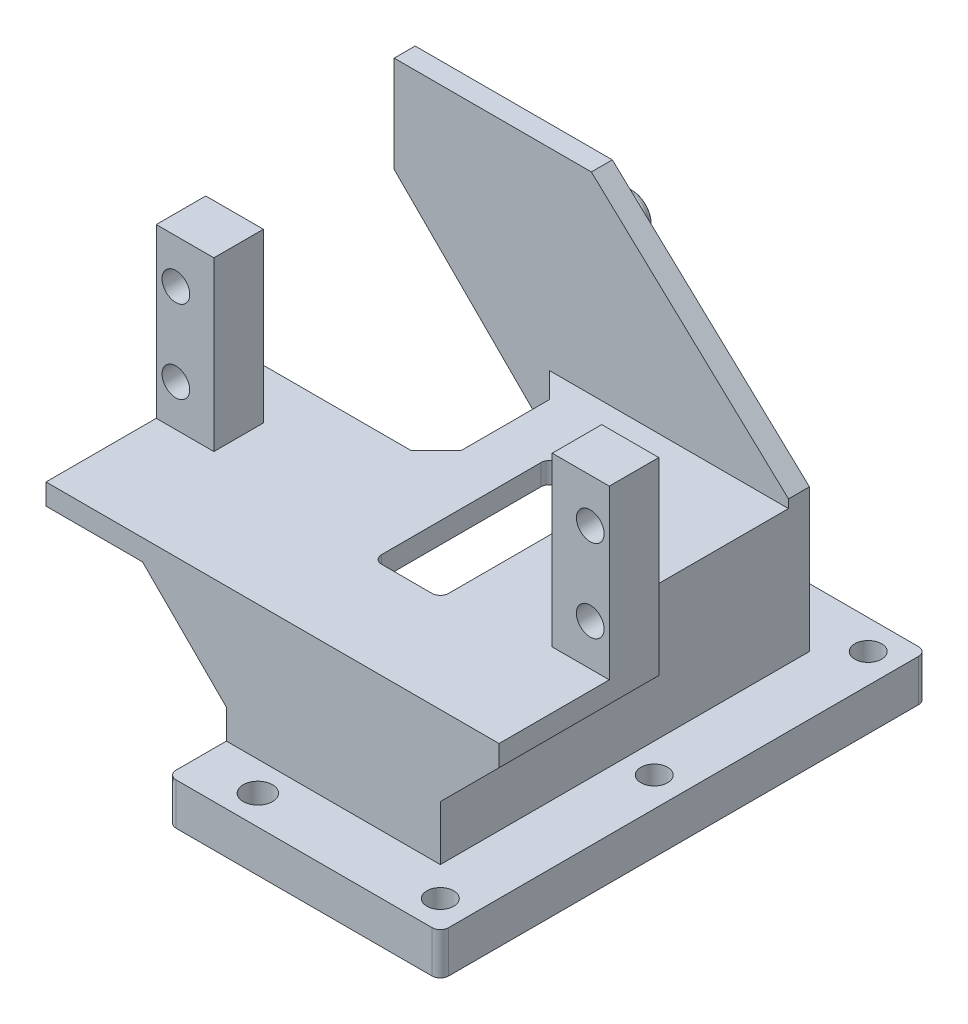
SolidWorks part; units mm, degrees
ref_plane "Front Plane" through (0, 0, 0) normal (0, 0, 1) x (1, 0, 0)
ref_plane "Top Plane" through (0, 0, 0) normal (0, 1, 0) x (1, 0, 0)
ref_plane "Right Plane" through (0, 0, 0) normal (1, 0, 0) x (0, 0, -1)
sketch "Sketch1" plane through (0, 0, 0) normal (0, 1, 0) x (1, 0, 0)
  line L0 (0, 40) -> (23, 40)
  line L1 (30, 0) -> (80, 0)
  line L2 (0, 20) -> (0, 40)
  line L3 (0, 100) -> (110, 100)
  line L4 (110, 20) -> (110, 40)
  line L5 (23, 40) -> (23, 79)
  line L6 (23, 79) -> (0, 79)
  line L7 (110, 79) -> (87, 79)
  line L8 (87, 79) -> (87, 40)
  line L9 (87, 40) -> (110, 40)
  line L10 (0, 79) -> (0, 100)
  line L11 (110, 79) -> (110, 100)
  line L12 (0, 20) -> (30, 0)
  line L13 (110, 20) -> (80, 0)
  point P0 (55, 0)
  dimension "D1" = 100
  dimension "D2" = 110
  dimension "23" = 23
  dimension "D4" = 40
  dimension "20" = 23
  dimension "D5" = 39
  dimension "40" = 40
extrude "Boss-Extrude1" add sketch "Sketch1" along normal blind 3.5
sketch "Sketch2" plane through (0, 3.5, 0) normal (0, 1, 0) x (1, 0, 0)
  line L0 (0, 79) -> (23, 79)
  line L1 (23, 79) -> (23, 40)
  line L2 (23, 40) -> (0, 40)
  line L3 (0, 40) -> (0, 37.5)
  line L4 (0, 40) -> (0, 20) construction
  line L5 (0, 37.5) -> (25.5, 37.5)
  line L6 (25.5, 37.5) -> (25.5, 81.5)
  line L7 (25.5, 81.5) -> (0, 81.5)
  line L8 (0, 100) -> (0, 79) construction
  line L9 (0, 81.5) -> (0, 79)
  line L10 (110, 81.5) -> (84.5, 81.5)
  line L11 (110, 79) -> (110, 100) construction
  line L12 (84.5, 81.5) -> (84.5, 37.5)
  line L13 (84.5, 37.5) -> (110, 37.5)
  line L14 (110, 20) -> (110, 40) construction
  line L15 (110, 37.5) -> (110, 40)
  line L16 (110, 40) -> (87, 40)
  line L17 (87, 40) -> (87, 79)
  line L18 (110, 81.5) -> (110, 79)
  line L19 (110, 79) -> (87, 79)
  dimension "D1" = 2.5
  dimension "3" = 2.5
  dimension "D2" = 2.5
  dimension "D3" = 2.5
  dimension "D4" = 2.5
  dimension "D5" = 2.5
extrude "Boss-Extrude2" add sketch "Sketch2" along normal blind 21
sketch "Sketch3" plane through (0, 24.5, 0) normal (0, 1, 0) x (1, 0, 0)
  line L1 (23, 79) -> (0, 79)
  line L2 (23, 79) -> (23, 40)
  line L3 (23, 40) -> (0, 40)
  line L4 (0, 79) -> (0, 40)
  line L5 (87, 79) -> (110, 79)
  line L6 (87, 79) -> (87, 40)
  line L7 (87, 40) -> (110, 40)
  line L8 (110, 79) -> (110, 40)
extrude "Boss-Extrude3" add sketch "Sketch3" against normal blind 2.5
sketch "Sketch5" plane through (0, 24.5, 0) normal (0, 1, 0) x (1, 0, 0)
  line L0 (55, 100) -> (55, 0) construction
  line L1 (110, 100) -> (0, 100) construction
  line L2 (30, 0) -> (80, 0) construction
  line L3 (110, 62.5) -> (131.5, 62.5)
  line L4 (0, 37.5) -> (-21.5, 37.5)
  line L5 (0, 37.5) -> (0, 62.5)
  line L6 (0, 62.5) -> (-21.5, 62.5)
  line L7 (-21.5, 37.5) -> (-21.5, 62.5)
  line L8 (131.5, 37.5) -> (131.5, 62.5)
  line L9 (110, 37.5) -> (131.5, 37.5)
  line L10 (110, 37.5) -> (110, 62.5)
  line L13 (25.5, 56.54) -> (25.5, 37.5)
  line L14 (25.5, 37.5) -> (32.57, 37.5)
  line L15 (32.57, 56.54) -> (32.57, 37.5)
  line L18 (84.5, 56.54) -> (84.5, 37.5)
  line L19 (84.5, 37.5) -> (77.43, 37.5)
  line L20 (77.43, 56.54) -> (77.43, 37.5)
  line L21 (25.5, 37.5) -> (25.5, 56.54) construction
  line L23 (25.5, 56.54) -> (32.57, 56.54)
  line L24 (77.43, 56.54) -> (84.5, 56.54) construction
  line L25 (84.5, 56.54) -> (77.43, 56.54)
  dimension "D1" = 21.5
  dimension "D2" = 25
extrude "Boss-Extrude5" add sketch "Sketch5" against normal blind 2.5
sketch "Sketch6" plane through (0, 24.5, 0) normal (0, 1, 0) x (1, 0, 0)
  line L0 (55, 100) -> (55, 0) construction
  line L1 (110, 100) -> (0, 100) construction
  line L2 (30, 0) -> (80, 0) construction
  line L3 (32.57, 37.5) -> (32.57, 56.54) construction
  line L4 (25.5, 56.54) -> (32.57, 56.54)
  line L5 (25.5, 56.54) -> (25.5, 50.64)
  line L6 (25.5, 50.64) -> (32.57, 50.64)
  line L7 (32.57, 56.54) -> (32.57, 50.64)
  line L8 (84.5, 50.64) -> (77.43, 50.64)
  line L9 (77.43, 56.54) -> (77.43, 50.64)
  line L10 (84.5, 56.54) -> (77.43, 56.54)
  line L11 (84.5, 56.54) -> (84.5, 50.64)
  line L12 (-21.5, 62.5) -> (-21.5, 37.5) construction
  line L13 (-21.5, 56.54) -> (-14.43, 56.54)
  line L14 (-21.5, 56.54) -> (-21.5, 50.64)
  line L15 (-21.5, 50.64) -> (-14.43, 50.64)
  line L16 (-14.43, 56.54) -> (-14.43, 50.64)
  line L17 (131.5, 50.64) -> (124.43, 50.64)
  line L18 (124.43, 56.54) -> (124.43, 50.64)
  line L19 (131.5, 56.54) -> (124.43, 56.54)
  line L20 (131.5, 56.54) -> (131.5, 50.64)
  dimension "D1" = 5.9
  dimension "D2" = 7.07
  dimension "D3" = 7.07
extrude "Boss-Extrude6" add sketch "Sketch6" along normal blind 20
sketch "Sketch7" plane through (0, 24.5, 0) normal (0, 1, 0) x (1, 0, 0)
  line L0 (55, 100) -> (55, 0) construction
  line L1 (110, 100) -> (0, 100) construction
  line L2 (30, 0) -> (80, 0) construction
  line L3 (25.5, 56.54) -> (25.5, 81.5) construction
  line L4 (0, 81.5) -> (25.5, 81.5)
  line L6 (0, 79) -> (25.5, 79)
  line L7 (25.5, 81.5) -> (25.5, 79)
  line L8 (110, 79) -> (84.5, 79)
  line L9 (84.5, 81.5) -> (84.5, 79)
  line L10 (110, 81.5) -> (84.5, 81.5)
  line L13 (0, 79) -> (-21.5, 79)
  line L15 (0, 81.5) -> (-21.5, 81.5)
  line L16 (-21.5, 79) -> (-21.5, 81.5)
  line L18 (110, 79) -> (131.5, 79)
  line L20 (110, 81.5) -> (131.5, 81.5)
  line L21 (131.5, 79) -> (131.5, 81.5)
  dimension "D1" = 2.5
extrude "Boss-Extrude7" add sketch "Sketch7" along normal blind 23
fillet "Fillet1" radius 10 4 edges at (0, 22, -38.75) (110, 22, -38.75) (0, 24.5, -80.25) (110, 24.5, -80.25) profile chamfer
sketch "Sketch9" plane through (0, 0, -81.5) normal (0, 0, -1) x (-1, 0, 0)
  line L0 (-131.5, 47.5) -> (-84.5, 47.5) construction
  line L3 (-131.5, 47.5) -> (-131.5, 24.5) construction
  line L4 (-55, 0) -> (-55, 48.0721) construction
  line L5 (-110, 0) -> (0, 0) construction
  circle A0 centre (-114.55, 34.35) radius 2.475
  circle A1 centre (4.55, 34.35) radius 2.475
  point P6 (-114.55, 34.35)
  dimension "D2" = 4.95
  dimension "D1" = 13.15
  dimension "D3" = 16.95
extrude "Boss-Extrude8" add sketch "Sketch9" along normal blind 9
fillet "Fillet2" radius 0.5 2 edges at (-2.075, 34.35, -90.5) (112.075, 34.35, -90.5)
sketch "Sketch10" plane through (0, 0, -50.64) normal (0, 0, 1) x (1, 0, 0)
  line L0 (55, 0) -> (55, 49.7444) construction
  line L1 (30, 0) -> (80, 0) construction
  line L2 (129.16, 44.5) -> (129.16, 24.5) construction
  line L3 (124.43, 44.5) -> (131.5, 44.5) construction
  line L4 (124.43, 24.5) -> (131.5, 24.5) construction
  line L5 (131.5, 44.5) -> (131.5, 24.5) construction
  line L6 (79.77, 44.5) -> (79.77, 24.5) construction
  line L7 (77.43, 44.5) -> (84.5, 44.5) construction
  line L8 (77.43, 24.5) -> (84.5, 24.5) construction
  line L9 (77.43, 44.5) -> (77.43, 24.5) construction
  circle A0 centre (129.16, 39.27) radius 1.65
  circle A1 centre (129.16, 29.43) radius 1.65
  circle A2 centre (79.77, 39.27) radius 1.65
  circle A3 centre (79.77, 29.43) radius 1.65
  circle A4 centre (-19.16, 29.43) radius 1.65
  circle A5 centre (-19.16, 39.27) radius 1.65
  circle A6 centre (30.23, 39.27) radius 1.65
  circle A7 centre (30.23, 29.43) radius 1.65
  dimension "D3" = 5.23
  dimension "D4" = 3.3
  dimension "D5" = 4.93
  dimension "D6" = 3.3
  dimension "D7" = 3.3
  dimension "D8" = 3.3
  dimension "D1" = 2.34
  dimension "D2" = 2.34
extrude "Cut-Extrude1" cut sketch "Sketch10" against normal blind 9
sketch "Sketch11" plane through (0, 0, -50.64) normal (0, 0, 1) x (1, 0, 0)
  line L0 (-21.5, 24.5) -> (-14.43, 24.5) construction
  line L1 (-14.43, 44.5) -> (-14.63, 44.5)
  line L2 (-14.43, 44.5) -> (-14.43, 24.5)
  line L3 (-14.43, 24.5) -> (-14.63, 24.5)
  line L4 (-14.63, 44.5) -> (-14.63, 24.5)
  line L5 (25.5, 24.5) -> (32.57, 24.5) construction
  line L6 (25.5, 44.5) -> (25.7, 44.5)
  line L7 (25.5, 44.5) -> (25.5, 24.5)
  line L8 (25.5, 24.5) -> (25.7, 24.5)
  line L9 (25.7, 44.5) -> (25.7, 24.5)
  line L10 (55, 3.5) -> (55, 47.4628) construction
  line L11 (30, 3.5) -> (80, 3.5) construction
  line L12 (84.5, 24.5) -> (84.3, 24.5)
  line L13 (84.3, 44.5) -> (84.3, 24.5)
  line L14 (84.5, 44.5) -> (84.3, 44.5)
  line L15 (84.5, 44.5) -> (84.5, 24.5)
  line L16 (124.43, 24.5) -> (124.63, 24.5)
  line L17 (124.63, 44.5) -> (124.63, 24.5)
  line L18 (124.43, 44.5) -> (124.63, 44.5)
  line L19 (124.43, 44.5) -> (124.43, 24.5)
  dimension "D1" = 0.2
  dimension "D2" = 0.2
extrude "Cut-Extrude2" cut sketch "Sketch11" against normal blind 9
sketch "Sketch12" plane through (0, 0, -81.5) normal (0, 0, -1) x (-1, 0, 0)
  line L0 (-108, 47.5) -> (-84.5, 25.5)
  line L1 (-131.5, 47.5) -> (-84.5, 47.5) construction
  line L2 (-84.5, 47.5) -> (-84.5, 3.5) construction
  line L3 (-84.5, 25.5) -> (-84.5, 47.5)
  line L4 (-84.5, 47.5) -> (-108, 47.5)
  line L5 (-55, 3.5) -> (-55, 47.5) construction
  line L6 (-110, 3.5) -> (0, 3.5) construction
  line L7 (-25.5, 25.5) -> (-25.5, 47.5)
  line L8 (-2, 47.5) -> (-25.5, 25.5)
  line L9 (-25.5, 47.5) -> (-2, 47.5)
  line L10 (-120, 24.5) -> (-131.5, 36)
  line L11 (-131.5, 47.5) -> (-131.5, 24.5) construction
  line L12 (-131.5, 36) -> (-131.5, 24.5)
  line L13 (-131.5, 24.5) -> (-120, 24.5)
  line L14 (10, 24.5) -> (21.5, 36)
  line L15 (21.5, 47.5) -> (21.5, 24.5) construction
  line L16 (21.5, 36) -> (21.5, 24.5)
  line L17 (21.5, 24.5) -> (10, 24.5)
extrude "Cut-Extrude3" cut sketch "Sketch12" against normal blind 9
fillet "Fillet3" radius 3 2 edges at (110, 23.25, -62.5) (0, 23.25, -62.5) profile chamfer
sketch "Sketch13" plane through (0, 3.5, 0) normal (0, 1, 0) x (1, 0, 0)
  line L0 (55, 100) -> (55, 0) construction
  line L1 (110, 100) -> (0, 100) construction
  line L2 (30, 0) -> (80, 0) construction
  line L3 (0, 30.5) -> (32.5, 30.5)
  line L4 (0, 37.5) -> (0, 20) construction
  line L5 (32.5, 30.5) -> (32.5, 88.5)
  line L6 (32.5, 88.5) -> (0, 88.5)
  line L7 (0, 100) -> (0, 81.5) construction
  line L8 (0, 88.5) -> (0, 81.5)
  line L9 (0, 81.5) -> (25.5, 81.5)
  line L10 (25.5, 81.5) -> (25.5, 37.5)
  line L11 (25.5, 37.5) -> (0, 37.5)
  line L12 (0, 37.5) -> (0, 30.5)
  line L13 (84.5, 37.5) -> (110, 37.5)
  line L14 (84.5, 81.5) -> (84.5, 37.5)
  line L15 (110, 81.5) -> (84.5, 81.5)
  line L16 (110, 88.5) -> (110, 81.5)
  line L17 (77.5, 88.5) -> (110, 88.5)
  line L18 (77.5, 30.5) -> (77.5, 88.5)
  line L19 (110, 30.5) -> (77.5, 30.5)
  line L20 (110, 37.5) -> (110, 30.5)
  dimension "D1" = 7
  dimension "D2" = 7
  dimension "D3" = 7
extrude "Boss-Extrude9" add sketch "Sketch13" along normal blind 5
sketch "Sketch14" plane through (0, 8.5, 0) normal (0, 1, 0) x (1, 0, 0)
  line L0 (55, 100) -> (55, 0) construction
  line L1 (110, 100) -> (0, 100) construction
  line L2 (30, 0) -> (80, 0) construction
  line L3 (0, 85) -> (29, 85) construction
  line L4 (0, 88.5) -> (0, 81.5) construction
  line L5 (29, 85) -> (29, 34) construction
  line L6 (29, 34) -> (0, 34) construction
  line L7 (0, 37.5) -> (0, 30.5) construction
  line L8 (32.5, 30.5) -> (32.5, 88.5) construction
  circle A0 centre (7.25, 34) radius 1.7478
  circle A3 centre (7.25, 85) radius 1.6
  circle A5 centre (29, 34) radius 1.6
  circle A6 centre (29, 59.5) radius 1.6
  circle A7 centre (29, 85) radius 1.6
  circle A8 centre (81, 34) radius 1.6
  circle A9 centre (102.75, 34) radius 1.7478
  circle A10 centre (81, 59.5) radius 1.6
  circle A11 centre (81, 85) radius 1.6
  circle A12 centre (102.75, 85) radius 1.6
  dimension "D2" = 3.2
  dimension "D3" = 7.25
  dimension "D4" = 3.2
  dimension "D6" = 3.2
  dimension "D7" = 7.25
  dimension "3.2" = 3.2
  dimension "D1" = 3.5
extrude "Cut-Extrude4" cut sketch "Sketch14" against normal blind 15
sketch "Sketch15" plane through (0, 0, -100) normal (0, 0, -1) x (-1, 0, 0)
  line L1 (0, 3.5) -> (-110, 3.5)
  line L2 (0, 3.5) -> (0, 0)
  line L3 (0, 0) -> (-110, 0)
  line L4 (-110, 3.5) -> (-110, 0)
  line L5 (-131.5, 47.5) -> (-32.5, 47.5)
  line L6 (-131.5, 47.5) -> (-131.5, 3.5)
  line L7 (-131.5, 3.5) -> (-32.5, 3.5)
  line L8 (-32.5, 47.5) -> (-32.5, 3.5)
  line M1 (-110, 0) -> (0, 0)
  line M2 (0, 0) -> (0, 3.5)
  line M3 (0, 3.5) -> (-110, 3.5)
  line M4 (-110, 3.5) -> (-110, 0)
extrude "Cut-Extrude5" cut sketch "Sketch15" against normal blind 113 contours L8 L5 L6 L7 L1 | L1 M4 M1 M2 M3 region at (55, 1.75, -100) region at (82, 25.5, -100)
fillet "Fillet4" radius 7 1 edges at (25.5, 22, -47.02) profile chamfer
fillet "Fillet5" radius 3 5 edges at (6.5, 22, -40) (23, 12.75, -40) (23, 12.75, -79) (11.5, 22, -79) (23, 22, -59.5) profile chamfer
fillet "Fillet6" radius 3 1 edges at (0, 21.75, -79) profile chamfer
fillet "Fillet7" radius 1 4 edges at (0, 6, -88.5) (0, 6, -30.5) (32.5, 6, -88.5) (32.5, 6, -30.5)
sketch "Sketch16" plane through (0, 22, 0) normal (0, -1, 0) x (1, 0, 0)
  line L0 (20, -76) -> (20, -43) construction
  line L1 (6, -49) -> (14, -49)
  line L2 (6, -49) -> (6, -70)
  line L3 (6, -70) -> (14, -70)
  line L4 (14, -49) -> (14, -70)
  line L5 (20, -43) -> (-10, -43) construction
  line L6 (0, -76) -> (0, -65.5) construction
  line L7 (0, -76) -> (20, -76) construction
  dimension "D1" = 6
  dimension "D2" = 6
  dimension "D3" = 6
  dimension "4" = 6
extrude "Cut-Extrude6" cut sketch "Sketch16" against normal blind 113
fillet "Fillet8" radius 1 4 edges at (14, 23.25, -70) (14, 23.25, -49) (6, 23.25, -70) (6, 23.25, -49)
